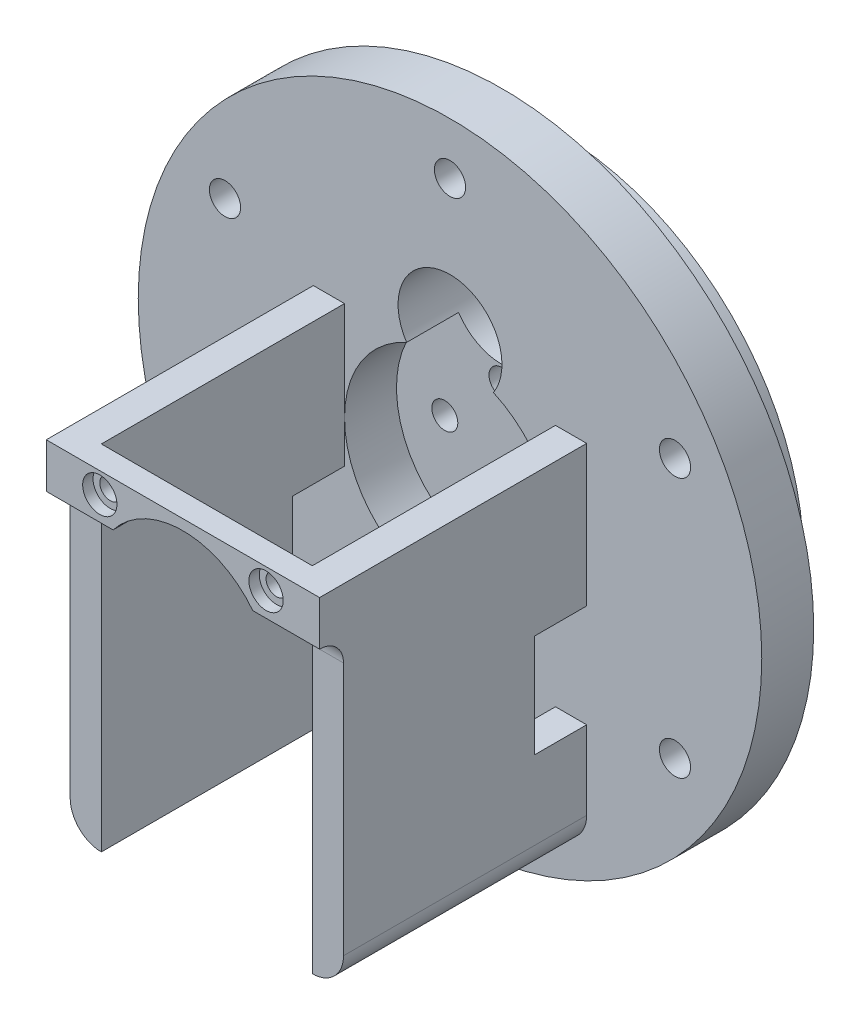
SolidWorks part; units mm, degrees
ref_plane "Alzado" through (0, 0, 0) normal (0, 0, 1) x (1, 0, 0)
ref_plane "Planta" through (0, 0, 0) normal (0, 1, 0) x (1, 0, 0)
ref_plane "Vista lateral" through (0, 0, 0) normal (1, 0, 0) x (0, 0, -1)
sketch "Croquis2" plane through (0, 0, 0) normal (0, 0, 1) x (1, 0, 0)
  circle A0 centre (0, 0) radius 30
  dimension "D1" = 60
extrude "Saliente-Extruir1" add sketch "Croquis2" along normal blind 5
sketch "Croquis6" plane through (0, 0, 0) normal (0, 0, -1) x (-1, 0, 0)
  circle A0 centre (0, 0) radius 23.5
  dimension "D1" = 47
extrude "Saliente-Extruir5" add sketch "Croquis6" along normal blind 5.5
sketch "Croquis7" plane through (0, 0, 5) normal (0, 0, 1) x (1, 0, 0)
  line L0 (0, 30) -> (0, -30) construction
  line L1 (10.15, 9.5) -> (2.9066, 9.5) construction
  line L2 (-13.15, -24.5) -> (-10.15, -24.5)
  line L3 (-13.15, -24.5) -> (-13.15, 9.5)
  line L4 (-13.15, 9.5) -> (-10.15, 9.5)
  line L5 (-10.15, -24.5) -> (-10.15, 9.5)
  line L6 (10.15, -24.5) -> (13.15, -24.5)
  line L7 (10.15, -24.5) -> (10.15, 9.5)
  line L8 (10.15, 9.5) -> (13.15, 9.5)
  line L9 (13.15, -24.5) -> (13.15, 9.5)
  line L10 (2.9066, 9.5) -> (2.9066, 0) construction
  circle A0 centre (0, 0) radius 30 construction
  dimension "D1" = 20.3
  dimension "D2" = 10.15
  dimension "D3" = 34
  dimension "D4" = 3
  dimension "D5" = 9.5
extrude "Saliente-Extruir6" add sketch "Croquis7" along normal blind 23.4
fillet "Redondeo1" radius 3 2 edges at (13.15, -24.5, 16.7) (-13.15, -24.5, 16.7)
sketch "Croquis8" plane through (0, 0, 5) normal (0, 0, 1) x (1, 0, 0)
  circle A0 centre (0, 0) radius 10.15
extrude "Cortar-Extruir1" cut sketch "Croquis8" against normal blind 5
sketch "Croquis9" plane through (0, 0, 0) normal (0, 0, 1) x (1, 0, 0)
  line L0 (10.15, 9.5) -> (10.15, 0) construction
  circle A0 centre (0, 5.5) radius 1.25
  circle A1 centre (5.5, 0) radius 1.25
  circle A2 centre (0, -5.5) radius 1.25
  circle A3 centre (-5.5, 0) radius 1.25
  point P14 (0, 0)
  dimension "D1" = 2.5
  dimension "D2" = 5.5
  dimension "D3" = 10.15
  dimension "D4" = 4
extrude "Cortar-Extruir2" cut sketch "Croquis9" against normal up to next
sketch "Croquis10" plane through (0, 0, 5) normal (0, 0, 1) x (1, 0, 0)
  circle A6 centre (21.6506, -12.5) radius 1.5
  circle A8 centre (-21.6506, -12.5) radius 1.5
  circle A9 centre (21.6506, 12.5) radius 1.5
  circle A10 centre (-21.6506, 12.5) radius 1.5
  circle A11 centre (0, 25) radius 1.5
  dimension "D1" = 3
extrude "Cortar-Extruir3" cut sketch "Croquis10" against normal blind 3.5
sketch "Croquis11" plane through (0, 0, 5) normal (0, 0, 1) x (1, 0, 0)
  circle A0 centre (0, 12) radius 4.9983
  circle A3 centre (0, 5.5) radius 1.25 construction
  dimension "D1" = 9.9967
  dimension "D3" = 6.5
  dimension "D2" = 12
extrude "Cortar-Extruir4" cut sketch "Croquis11" against normal up to next
sketch "Croquis12" plane through (13.15, 0, 0) normal (1, 0, 0) x (0, 0, -1)
  line L2 (-28.4, -21.5) -> (-5, -21.5) construction
  line L4 (-5, -13.95) -> (-5, -4.05)
  line L5 (-5, -21.5) -> (-5, 9.5) construction
  line L6 (-5, -4.05) -> (-10, -4.05)
  line L7 (-10, -13.95) -> (-10, -4.05)
  line L8 (-10, -13.95) -> (-5, -13.95)
  dimension "D1" = 5
  dimension "D2" = 9.9
  dimension "D3" = 7.55
extrude "Cortar-Extruir5" cut sketch "Croquis12" against normal up to surface (26.3 mm away) up to face at (-13.15, -6, 16.7)
sketch "Croquis13" plane through (0, 0, 28.4) normal (0, 0, 1) x (1, 0, 0)
  line L6 (0, 30) -> (0, -30) construction
  line L7 (-13.15, 9.5) -> (-13.15, -21.5) construction
  line L8 (-13.15, 9.5) -> (13.15, 9.5)
  line L9 (-13.15, 9.5) -> (-13.15, 5.2)
  line L10 (-13.15, 5.2) -> (13.15, 5.2)
  line L11 (13.15, 9.5) -> (13.15, 5.2)
  line L12 (13.15, -21.5) -> (13.15, 9.5) construction
  line L13 (-10.15, 9.5) -> (-13.15, 9.5) construction
  circle A0 centre (0, 0) radius 30 construction
  dimension "D1" = 4.3
extrude "Saliente-Extruir7" add sketch "Croquis13" along normal blind 2.3
fillet "Redondeo2" radius 2.3 2 edges at (11.65, 5.2, 28.4) (-11.65, 5.2, 28.4)
sketch "Croquis15" plane through (0, 0, 30.7) normal (0, 0, 1) x (1, 0, 0)
  line L0 (-6.0795, 5.2) -> (6.0795, 5.2) construction
  line L1 (-10.15, 5.2) -> (10.15, 5.2) construction
  line L2 (-7.0824, 4.7) -> (7.0824, 4.7)
  arc A0 (-6.0795, 5.2) -> (6.0795, 5.2) centre (0, 0) cw construction
  arc A1 (-7.0824, 4.7) -> (7.0824, 4.7) centre (0, 0) cw
  dimension "D1" = 8
  dimension "D3" = 0.5
  dimension "D2" = 12.1589
extrude "Cortar-Extruir6" cut sketch "Croquis15" against normal blind 2.3
sketch "Croquis16" plane through (0, 0, 30.7) normal (0, 0, 1) x (1, 0, 0)
  line L0 (-13.15, 9.5) -> (-13.15, 5.2) construction
  line L1 (13.15, 9.5) -> (-13.15, 9.5) construction
  line L2 (13.15, 5.2) -> (13.15, 9.5) construction
  circle A2 centre (-8, 7.5) radius 1
  circle A3 centre (8, 7.5) radius 1
  point P4 (-9, 7.6776)
  point P12 (7, 7.7093)
  dimension "D3" = 1
  dimension "D6" = 1
  dimension "D1" = 5.15
  dimension "D2" = 2
  dimension "D4" = 2
  dimension "D5" = 5.15
extrude "Cortar-Extruir7" cut sketch "Croquis16" against normal blind 2.3
sketch "Croquis17" plane through (0, 0, 30.7) normal (0, 0, 1) x (1, 0, 0)
  circle A0 centre (8, 7.5) radius 1 construction
  circle A1 centre (-8, 7.5) radius 1 construction
  circle A2 centre (8, 7.5) radius 1 construction
  circle A3 centre (-8, 7.5) radius 1 construction
  circle A4 centre (-8, 7.5) radius 1.65
  circle A5 centre (8, 7.5) radius 1.65
  dimension "D1" = 0.65
extrude "Cortar-Extruir8" cut sketch "Croquis17" against normal blind 1
